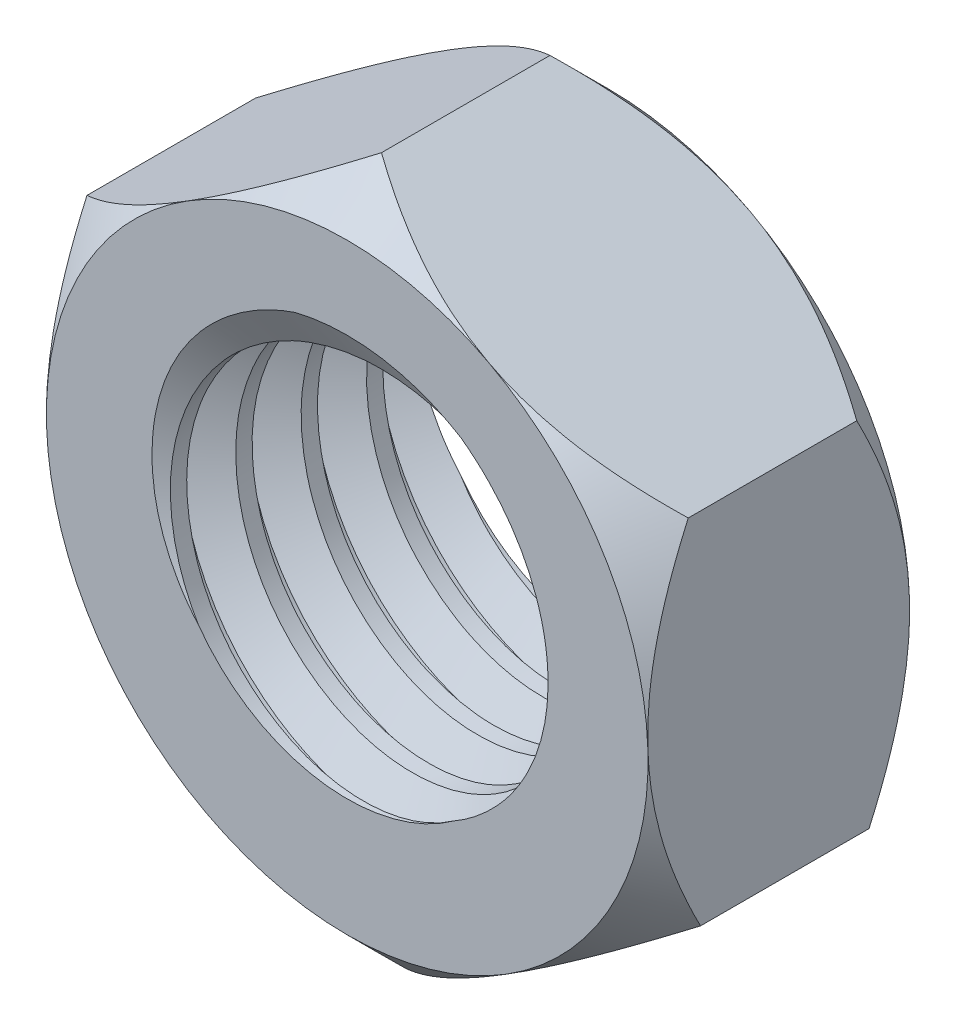
SolidWorks part; units mm, degrees
ref_plane "Front Plane" through (0, 0, 0) normal (0, 0, 1) x (1, 0, 0)
ref_plane "Top Plane" through (0, 0, 0) normal (0, 1, 0) x (1, 0, 0)
ref_plane "Right Plane" through (0, 0, 0) normal (1, 0, 0) x (0, 0, -1)
sketch "Sketch1" plane through (0, 0, 0) normal (0, 0, 1) x (1, 0, 0)
  line L1 (5.8637, -3.1145) -> (5.6291, 3.5208)
  line L2 (5.6291, 3.5208) -> (-0.2346, 6.6354)
  line L3 (-0.2346, 6.6354) -> (-5.8637, 3.1145)
  line L4 (-5.8637, 3.1145) -> (-5.6291, -3.5208)
  line L5 (-5.6291, -3.5208) -> (0.2346, -6.6354)
  line L6 (0.2346, -6.6354) -> (5.8637, -3.1145)
  circle A0 centre (0, 0) radius 5.75 construction
  dimension "D1" = 11.5
extrude "Boss-Extrude1" add sketch "Sketch1" along normal mid plane 5 contours L3 L4 L5 L6 L1 L2
sketch "Sketch5" plane through (0, 0, 2.5) normal (0, 0, 1) x (1, 0, 0)
  circle A0 centre (0, 0) radius 3.5
  dimension "D1" = 7
extrude "Cut-Extrude2" cut sketch "Sketch5" against normal blind 9
thread "Thread1" pitch 1.25 method cut profile "Thread Profile1" start angle 0, offset 2, length 12, pitch 1.25, diameter 7
ref_plane "Plane1" through (3.5, 0, -4.5) normal (0, -1, 0) x (1, 0, 0)
sketch "Thread Profile1" plane through (3.5, 0, -4.5) normal (0, -1, 0) x (1, 0, 0)
  line L0 (0, 0) -> (0, 1.25) construction
  line L1 (0, 0) -> (0.6766, 0.3906)
  line L2 (0.6766, 0.3906) -> (0.6766, 0.5469)
  line L3 (0.6766, 0.5469) -> (0, 0.9375)
  line L4 (0.6766, 0.4687) -> (0, 0.4687) construction
  line L11 (0, 0) -> (0, 0.9375)
  point P2 (0, 0)
  dimension "Pitch" = 1.25
  dimension "Profile_Angle" = 60
  dimension "Profile_Land" = 0.1562
  dimension "Profile_Height" = 0.6766
sketch "Sketch6" plane through (0, 0, 2.5) normal (0, 0, 1) x (1, 0, 0)
  circle A0 centre (0, 0) radius 5.75
extrude "Cut-Extrude3" cut sketch "Sketch6" against normal mid plane 10 draft 45 flip side to cut
mirror "Mirror1" about plane through (0, 0, 0) normal (0, 0, 1) of "Cut-Extrude3"
